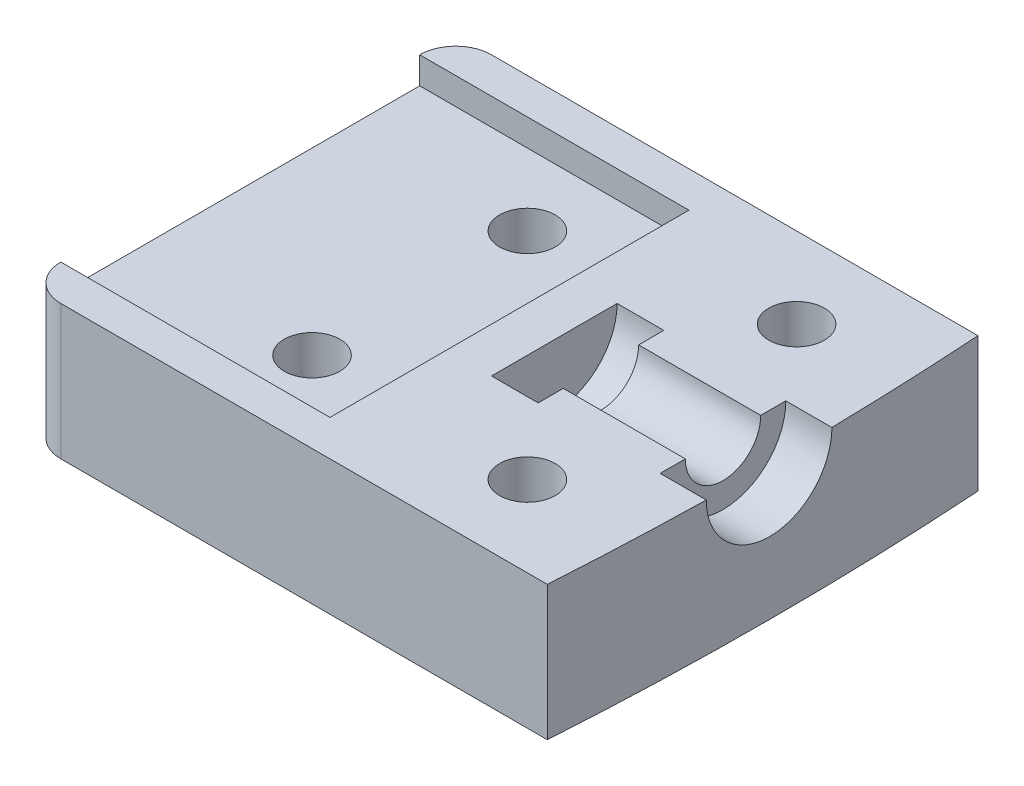
SolidWorks part; units mm, degrees
ref_plane "Front Plane" through (0, 0, 0) normal (0, 0, 1) x (1, 0, 0)
ref_plane "Top Plane" through (0, 0, 0) normal (0, 1, 0) x (1, 0, 0)
ref_plane "Right Plane" through (0, 0, 0) normal (1, 0, 0) x (0, 0, -1)
sketch "Sketch1" plane through (0, 0, 0) normal (0, 1, 0) x (1, 0, 0)
  line L0 (0, 0) -> (-180, 0) construction
  line L1 (0, -12) -> (-25, -12)
  line L2 (0, -12) -> (0, 12)
  line L3 (0, 12) -> (-25, 12)
  line L4 (-25, -12) -> (-25, 12)
  line L5 (-180, 0) -> (4.5, 0) construction
  line L6 (0, 12) -> (4.1093, 12)
  line L7 (0, -12) -> (4.1093, -12)
  line L8 (-180, 0) -> (5, 0) construction
  arc A0 (4.1093, -12) -> (4.1093, 12) centre (-180, 0) ccw
  circle A1 centre (-180, 0) radius 185 construction
  point P4 (0, 0)
  dimension "D4" = 184.5
  dimension "D5" = 185
  dimension "D1" = 25
  dimension "D2" = 24
  dimension "D3" = 180
extrude "Boss-Extrude1" add sketch "Sketch1" along normal blind 10 contours L4 L1 L2 L3 | L7 A0 L6 L2 region at (-12.5, 0, 0) region at (2.1865, 0, 0)
sketch "Sketch2" plane through (0, 10, 0) normal (0, 1, 0) x (1, 0, 0)
  line L1 (-25, -12) -> (-25, 12) construction
  line L2 (-25, 10) -> (-10, 10)
  line L3 (-25, 10) -> (-25, -10)
  line L4 (-25, -10) -> (-10, -10)
  line L5 (-10, 10) -> (-10, -10)
  point P0 (-25, 0)
  point P7 (-25, 0)
  dimension "D1" = 20
  dimension "D2" = 15
extrude "Cut-Extrude1" cut sketch "Sketch2" against normal blind 1.5
sketch "Sketch3" plane through (0, 10, 0) normal (0, 1, 0) x (1, 0, 0)
  line L0 (5, 0) -> (-7.5, 0) construction
  line L1 (0, 0) -> (-180, 0) construction
  dimension "D1" = 12.5
ref_plane "shaft" through (-7.5, 0, 0) normal (1, 0, 0) x (0, 0, -1)
sketch "Sketch4" plane through (-7.5, 0, 0) normal (1, 0, 0) x (0, 0, -1)
  line L0 (12, 10) -> (-12, 10) construction
  circle A0 centre (0, 10) radius 2.1
  dimension "D1" = 4.2
extrude "Cut-Extrude2" cut sketch "Sketch4" along normal through all
fillet "Fillet1" radius 2 2 edges at (-25, 5, -12) (-25, 5, 12)
sketch "Sketch5" plane through (-7.5, 0, 0) normal (1, 0, 0) x (0, 0, -1)
  line L0 (-2.1, 10) -> (2.1, 10) construction
  circle A0 centre (0, 10) radius 3.5
  dimension "D1" = 7
extrude "Cut-Extrude3" cut sketch "Sketch5" along normal blind 2.6
sketch "Sketch7" plane through (-7.5, 0, 0) normal (1, 0, 0) x (0, 0, -1)
  line L0 (-3.5, 10) -> (3.5, 10) construction
  circle A0 centre (0, 10) radius 2.5
  dimension "D1" = 5
extrude "Cut-Extrude4" [suppressed] cut sketch "Sketch7" against normal blind 0.2 and the other way blind 2.7
ref_plane "Plane2" through (0, 10, 0) normal (0, 1, 0) x (1, 0, 0)
sketch "Sketch8" plane through (0, 10, 0) normal (0, 1, 0) x (1, 0, 0)
  line L0 (0, 0) -> (4.5, 0) construction
  line L2 (1.9, 0) -> (4.5, 0)
  line L3 (1.9, 0) -> (1.9, 3.5)
  line L4 (1.9, 3.5) -> (4.5, 3.5)
  line L5 (4.5, 0) -> (4.5, 3.5)
  arc A0 (4.488, -2.1) -> (4.488, 2.1) centre (-180, 0) ccw construction
  dimension "D1" = 2.6
  dimension "D2" = 7
revolve "Cut-Revolve1" cut sketch "Sketch8" angle 360 about L0
sketch "Sketch9" plane through (1.9, 0, 0) normal (1, 0, 0) x (0, 0, -1)
  circle A0 centre (0, 10) radius 2.5
  dimension "D1" = 5
extrude "Cut-Extrude5" [suppressed] cut sketch "Sketch9" against normal up to surface (9.7 mm away) up to face at (-25, 4.25, 0)
sketch "Sketch11" plane through (0, 8.5, 0) normal (0, 1, 0) x (1, 0, 0)
  circle A0 centre (-15, -6) radius 1.5 construction
  circle A1 centre (-15, 6) radius 1.5 construction
  circle A2 centre (-15, -6) radius 1.5 construction
  circle A3 centre (-15, 6) radius 1.5 construction
hole_wizard "Ø3.1 (3.1) Diameter Hole1" positions "Sketch12" profile "Sketch13" hole size "Ø3.1" standard "ISO" end condition through all
sketch "Sketch12" plane through (0, 8.5, 0) normal (0, 1, 0) x (1, 0, 0)
  point P0 (-15, 6)
  point P3 (-15, -6)
sketch "Sketch13" plane through (-15, 8.5, -6) normal (1, 0, 0) x (0, 0, 1)
  line L0 (0, 0) -> (0, 8.5)
  line L1 (0, 8.5) -> (1.55, 8.5)
  line L2 (1.55, 8.5) -> (1.55, 0)
  line L5 (1.55, 0) -> (0, 0)
  line L11 (0, -6.35) -> (0, 107.95) construction
  dimension "Thru Hole Dia." = 3.1
  dimension "Thru Hole Depth" = 8.5
sketch "Sketch14" plane through (0, 10, 0) normal (0, 1, 0) x (1, 0, 0)
  line L0 (-10, 0) -> (0, 0) construction
  line L1 (-10, -10) -> (-10, 10) construction
  line L2 (-1.5, 12) -> (-1.5, -12) construction
  line L3 (4.1093, 12) -> (-23, 12) construction
  line L4 (4.1093, -12) -> (-23, -12) construction
  point P7 (-1.5, -7.5)
  point P13 (-1.5, 7.5)
  dimension "D1" = 8.5
  dimension "D2" = 15
hole_wizard "Ø3.1 (3.1) Diameter Hole2" positions "Sketch15" profile "Sketch16" hole size "Ø3.1" standard "ISO" end condition through all
sketch "Sketch15" plane through (0, 10, 0) normal (0, 1, 0) x (1, 0, 0)
  point P0 (-1.5, 7.5)
  point P3 (-1.5, -7.5)
sketch "Sketch16" plane through (-1.5, 10, -7.5) normal (1, 0, 0) x (0, 0, 1)
  line L0 (0, 0) -> (0, 10)
  line L1 (0, 10) -> (1.55, 10)
  line L2 (1.55, 10) -> (1.55, 0)
  line L5 (1.55, 0) -> (0, 0)
  line L11 (0, -6.35) -> (0, 107.95) construction
  dimension "Thru Hole Dia." = 3.1
  dimension "Thru Hole Depth" = 10
sketch "Sketch17" plane through (0, 0, 0) normal (0, -1, 0) x (1, 0, 0)
  line L3 (-25, 10) -> (-25, -10)
  line L4 (-23, -12) -> (4.1093, -12)
  line L5 (4.1093, 12) -> (-23, 12)
  line L6 (-25, 10) -> (-25, -10)
  line L7 (-23, -12) -> (4.1093, -12)
  line L8 (4.1093, 12) -> (-23, 12)
  arc A3 (-25, -10) -> (-23, -12) centre (-23, -10) ccw
  arc A4 (4.1093, -12) -> (4.1093, 12) centre (-180, 0) ccw
  arc A5 (-23, 12) -> (-25, 10) centre (-23, 10) ccw
  arc A6 (-25, -10) -> (-23, -12) centre (-23, -10) ccw
  arc A7 (4.1093, -12) -> (4.1093, 12) centre (-180, 0) ccw
  arc A8 (-23, 12) -> (-25, 10) centre (-23, 10) ccw
  dimension "D1" = 0
extrude "Cut-Extrude6" cut sketch "Sketch17" against normal blind 2.5
